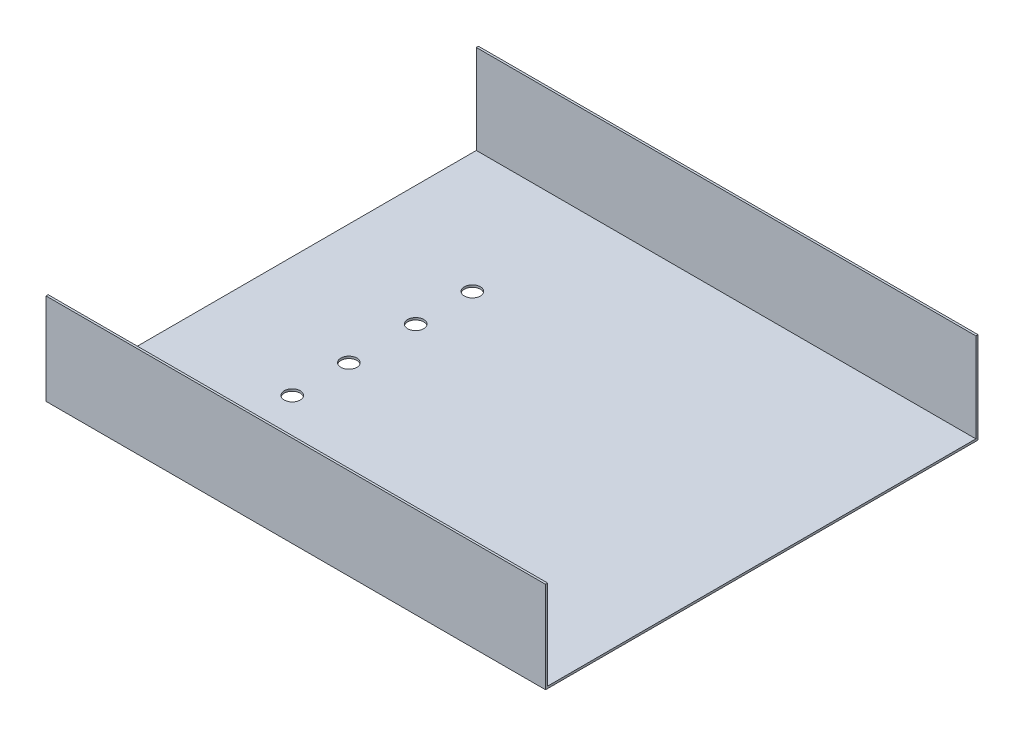
SolidWorks part; units mm, degrees
material "AISI 304"
ref_plane "Alzado" through (0, 0, 0) normal (0, 0, 1) x (1, 0, 0)
ref_plane "Planta" through (0, 0, 0) normal (0, 1, 0) x (1, 0, 0)
ref_plane "Vista lateral" through (0, 0, 0) normal (1, 0, 0) x (0, 0, -1)
sketch "Croquis1" plane through (0, 0, 0) normal (1, 0, 0) x (0, 0, -1)
  line L0 (0, 25) -> (0, 0)
  line L1 (0, 0) -> (120, 0)
  line L2 (120, 0) -> (120, 25)
  line L3 (0, 25) -> (120, 25)
  dimension "D1" = 120
  dimension "D2" = 25
extrude "Saliente-Extruir1" add sketch "Croquis1" along normal blind 140
shell "Vaciado1" thickness 0.6 removed face at (0, 12.5, -60) removed face at (140, 12.5, -60) removed face at (70, 25, -60) outward yes
hole_wizard "Taladro de margen para M41" positions "Croquis2" profile "Croquis3" hole size "M4" standard "Ansi Metric"
sketch "Croquis2" plane through (83.2595, 0, -172.6309) normal (0, 1, 0) x (1, 0, 0)
  point P0 (-49.6094, -137.8684)
  point P3 (-49.6095, -87.3934)
  point P6 (-49.6095, -103.2684)
  point P11 (-49.6094, -121.9934)
sketch "Croquis3" plane through (33.65, 0, -34.7625) normal (1, 0, 0) x (0, 0, 1)
  line L0 (0, 0) -> (0, 0.599)
  line L1 (0, 0.599) -> (2.25, 0.599)
  line L2 (2.25, 0.599) -> (2.25, 0)
  line L5 (2.25, 0) -> (0, 0)
  line L11 (0, -6.35) -> (0, 107.95) construction
  dimension "Diámetro de taladro hasta el siguiente" = 4.5
  dimension "Profundidad de taladro hasta el siguiente" = 0.599
